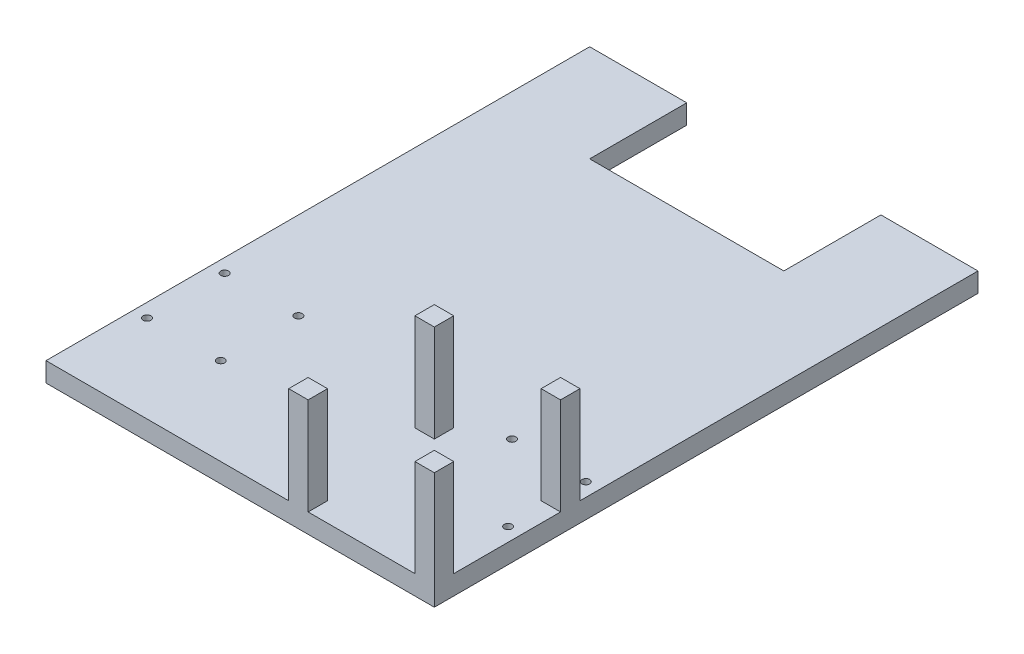
SolidWorks part; units mm, degrees
material "Pine"
ref_plane "Front Plane" through (0, 0, 0) normal (0, 0, 1) x (1, 0, 0)
ref_plane "Top Plane" through (0, 0, 0) normal (0, 1, 0) x (1, 0, 0)
ref_plane "Right Plane" through (0, 0, 0) normal (1, 0, 0) x (0, 0, -1)
sketch "Sketch3" plane through (0, 0, 0) normal (0, 1, 0) x (1, 0, 0)
  line L1 (-100, -140) -> (100, -140)
  line L2 (-100, -140) -> (-100, 140)
  line L3 (-100, 140) -> (100, 140)
  line L4 (100, -140) -> (100, 140)
  line L5 (-100, -140) -> (100, 140) construction
  line L6 (-100, 140) -> (100, -140) construction
  point P0 (0, 0)
  dimension "D1" = 200
  dimension "D2" = 280
extrude "Boss-Extrude1" add sketch "Sketch3" along normal blind 10
sketch "Sketch4" plane through (0, 10, 0) normal (0, 1, 0) x (1, 0, 0)
  line L0 (100, -140) -> (100, 140) construction
  line L1 (100, -140) -> (90, -140)
  line L2 (100, -140) -> (100, -130)
  line L3 (100, -65) -> (90, -65)
  line L4 (25, -140) -> (25, -130)
  line L5 (-100, -140) -> (100, -140) construction
  line L6 (35, -140) -> (35, -130)
  line L7 (90, -65) -> (90, -75)
  line L8 (35, -65) -> (25, -65)
  line L9 (35, -140) -> (25, -140)
  line L10 (25, -130) -> (35, -130)
  line L11 (25, -75) -> (35, -75)
  line L12 (90, -75) -> (100, -75)
  line L13 (90, -130) -> (100, -130)
  line L14 (25, -75) -> (25, -65)
  line L15 (35, -75) -> (35, -65)
  line L16 (90, -130) -> (90, -140)
  line L17 (100, -75) -> (100, -65)
  point P20 (95, -130)
  dimension "D1" = 0
  dimension "D2" = 0
  dimension "D3" = 75
  dimension "D4" = 75
  dimension "D5" = 10
  dimension "D6" = 10
  dimension "D7" = 10
  dimension "D8" = 10
  dimension "D9" = 10
extrude "Boss-Extrude2" add sketch "Sketch4" along normal blind 50
sketch "Sketch7" plane through (0, 0, 0) normal (0, -1, 0) x (1, 0, 0)
  line L0 (100, 140) -> (100, -140) construction
  line L1 (-100, 140) -> (100, 140) construction
  line L4 (-93, 55) -> (93, 55) construction
  line L5 (-93, 95) -> (93, 95) construction
  line L6 (-100, -140) -> (-100, 140) construction
  circle A8 centre (-93, 55) radius 2
  circle A9 centre (-93, 95) radius 2
  circle A10 centre (-55, 95) radius 2
  circle A11 centre (-55, 55) radius 2
  circle A12 centre (55, 95) radius 2
  circle A13 centre (93, 95) radius 2
  circle A14 centre (93, 55) radius 2
  circle A15 centre (55, 55) radius 2
  dimension "D17" = 40
  dimension "D4" = 7
  dimension "D1" = 38
  dimension "D2" = 40
  dimension "D3" = 38
  dimension "D5" = 38
  dimension "D6" = 40
  dimension "D7" = 38
  dimension "D16" = 7
  dimension "D18" = 55.1725
  dimension "D19" = 40
  dimension "D20" = 55.1725
  dimension "D27" = 45
extrude "Cut-Extrude2" cut sketch "Sketch7" against normal blind 10
sketch "Sketch8" plane through (0, 10, 0) normal (0, 1, 0) x (1, 0, 0)
  line L0 (-100, -140) -> (25, -140) construction
  line L1 (-100, 140) -> (-100, -140) construction
  line L2 (100, -65) -> (100, 140) construction
  circle A0 centre (-35, -35) radius 4
  circle A1 centre (-15, -35) radius 4
  circle A5 centre (-35, 40) radius 4
  circle A6 centre (-15, 40) radius 4
  circle A7 centre (45, 2.5) radius 4
  circle A8 centre (65, 2.5) radius 4
  dimension "D1" = 8
  dimension "D2" = 8
  dimension "D4" = 8
  dimension "D5" = 8
  dimension "D7" = 8
  dimension "D8" = 8
  dimension "D3" = 20
  dimension "D6" = 20
  dimension "D9" = 20
  dimension "D10" = 105
  dimension "D11" = 65
  dimension "D12" = 65
  dimension "D13" = 75
  dimension "D14" = 37.5
  dimension "D15" = 35
extrude "Cut-Extrude3" [suppressed] cut sketch "Sketch8" against normal blind 10
sketch "Sketch9" plane through (0, 10, 0) normal (0, 1, 0) x (1, 0, 0)
  line L0 (100, 140) -> (-100, 140) construction
  line L1 (50, 140) -> (-50, 140)
  line L2 (50, 140) -> (50, 90)
  line L3 (50, 90) -> (-50, 90)
  line L4 (-50, 140) -> (-50, 90)
  line L5 (50, 98.4245) -> (100, 98.4245) construction
  line L6 (100, -65) -> (100, 140) construction
  line L7 (-50, 98.4245) -> (-100, 98.4245) construction
  line L8 (-100, 140) -> (-100, -140) construction
  dimension "D1" = 100
  dimension "D2" = 50
extrude "Cut-Extrude4" cut sketch "Sketch9" against normal blind 10
